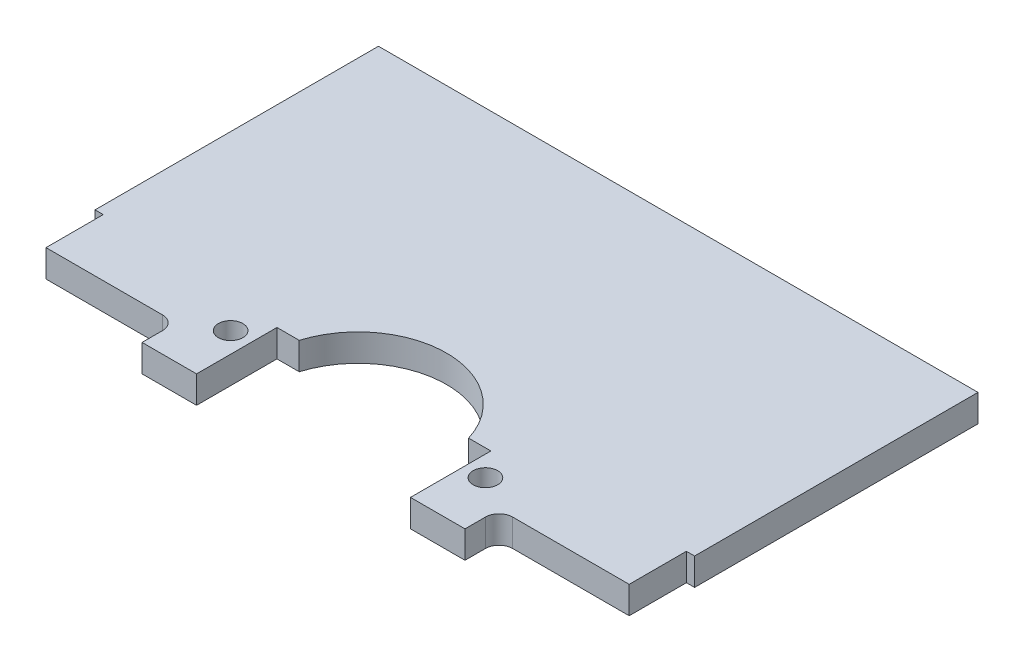
SolidWorks part; units mm, degrees
ref_plane "Front Plane" through (0, 0, 0) normal (0, 0, 1) x (1, 0, 0)
ref_plane "Top Plane" through (0, 0, 0) normal (0, 1, 0) x (1, 0, 0)
ref_plane "Right Plane" through (0, 0, 0) normal (1, 0, 0) x (0, 0, -1)
sketch "Sketch1" plane through (0, 0, 0) normal (0, 1, 0) x (1, 0, 0)
  line L0 (0, 0) -> (0, -20.1295) construction
  line L1 (-27.94, -13.208) -> (27.94, -13.208)
  line L2 (-27.94, -13.208) -> (-27.94, 13.208)
  line L3 (-27.94, 13.208) -> (27.94, 13.208)
  line L4 (27.94, -13.208) -> (27.94, 13.208)
  line L5 (-27.94, -13.208) -> (27.94, 13.208) construction
  line L6 (-27.94, 13.208) -> (27.94, -13.208) construction
  line L7 (-9.9695, -21.717) -> (-9.9695, -14.224)
  line L8 (-27.178, -18.542) -> (27.178, -18.542)
  line L9 (-27.178, -18.542) -> (-27.178, -13.208)
  line L10 (-27.178, -13.208) -> (27.178, -13.208)
  line L11 (27.178, -18.542) -> (27.178, -13.208)
  line L12 (-27.178, -18.542) -> (27.178, -13.208) construction
  line L13 (-27.178, -13.208) -> (27.178, -18.542) construction
  line L14 (-15.0495, -21.717) -> (15.0495, -21.717)
  line L15 (-15.0495, -21.717) -> (-15.0495, -18.542)
  line L16 (-15.0495, -18.542) -> (15.0495, -18.542)
  line L17 (15.0495, -21.717) -> (15.0495, -18.542)
  line L18 (-15.0495, -21.717) -> (15.0495, -18.542) construction
  line L19 (-15.0495, -18.542) -> (15.0495, -21.717) construction
  line L20 (-9.9695, -14.224) -> (9.9695, -14.224)
  line L21 (9.9695, -14.224) -> (9.9695, -21.717)
  line L22 (-11.8745, -21.717) -> (-11.8745, -16.637) construction
  line L23 (11.8745, -21.717) -> (11.8745, -16.637) construction
  line L24 (-11.8745, -16.637) -> (11.8745, -16.637) construction
  circle A0 centre (-11.8745, -16.637) radius 1.143
  circle A1 centre (11.8745, -16.637) radius 1.143
  arc A2 (-7.8945, -14.224) -> (7.8945, -14.224) centre (0, -16.637) cw
  point P0 (0, 0)
  point P8 (0, -15.875)
  dimension "D11" = 2.286
  dimension "D12" = 8.255
  dimension "D1" = 55.88
  dimension "D2" = 26.416
  dimension "D3" = 31.75
  dimension "D4" = 0.762
  dimension "D5" = 34.925
  dimension "D6" = 27.432
  dimension "D7" = 19.939
  dimension "D8" = 5.08
  dimension "D9" = 3.175
  dimension "D10" = 5.08
extrude "Boss-Extrude1" add sketch "Sketch1" along normal blind 2.54 contours L1 A2 L4 L3 L2 | L20 A2 L1 L9 L8 L7 A0 | L1 A2 L20 L21 L16 L8 L11 A1 | L15 L14 L7 L8 | L16 L21 L14 L17 region at (0, 0, -0.4105) region at (-18.6315, 0, 15.7849) region at (18.6315, 0, 15.7849) region at (-12.5095, 0, 20.1295) region at (12.5095, 0, 20.1295)
fillet "Fillet1" radius 1.27 2 edges at (-15.0495, 1.27, 18.542) (15.0495, 1.27, 18.542)
sketch "hours" plane through (0, 2.54, 0) normal (0, 1, 0) x (1, 0, 0)
  line L0 (0, 0) -> (0, -16.1969) construction
  line L1 (-17.3899, 1.193) -> (-15.3064, -0.8905)
  line L2 (15.3064, -0.8905) -> (17.3899, 1.193)
  line L3 (-7.4579, 1.808) -> (-8.5432, 4.4283)
  line L4 (7.4579, 1.808) -> (8.5432, 4.4283)
  line L5 (0, 2.6059) -> (0, 5.3999)
  line L6 (-13.7582, 1.7332) -> (-12.6317, 0.2651)
  line L7 (-10.9298, 2.7341) -> (-10.0169, 1.1528)
  line L8 (-5.4082, 3.9869) -> (-4.9448, 2.2574)
  line L9 (-2.6966, 4.2856) -> (-2.4641, 2.5197)
  line L10 (2.6966, 4.2856) -> (2.4641, 2.5197)
  line L11 (5.4082, 3.9869) -> (4.9448, 2.2574)
  line L12 (10.9298, 2.7341) -> (10.0169, 1.1528)
  line L13 (13.7582, 1.7332) -> (12.6317, 0.2651)
  line L31 (-27.94, -13.208) -> (-27.178, -13.208)
  line L32 (-27.178, -13.208) -> (-27.178, -18.542)
  line L33 (-27.178, -18.542) -> (-16.3195, -18.542)
  line L34 (-15.0495, -19.812) -> (-15.0495, -21.717)
  line L35 (-15.0495, -21.717) -> (-9.9695, -21.717)
  line L36 (-9.9695, -21.717) -> (-9.9695, -14.224)
  line L37 (-9.9695, -14.224) -> (-7.8945, -14.224)
  line L38 (7.8945, -14.224) -> (9.9695, -14.224)
  line L39 (9.9695, -14.224) -> (9.9695, -21.717)
  line L40 (9.9695, -21.717) -> (15.0495, -21.717)
  line L41 (15.0495, -21.717) -> (15.0495, -19.812)
  line L42 (16.3195, -18.542) -> (27.178, -18.542)
  line L43 (27.178, -18.542) -> (27.178, -13.208)
  line L44 (27.178, -13.208) -> (27.94, -13.208)
  line L45 (27.94, -13.208) -> (27.94, 13.208)
  line L46 (27.94, 13.208) -> (-27.94, 13.208)
  line L47 (-27.94, 13.208) -> (-27.94, -13.208)
  line L48 (-27.94, -13.208) -> (-27.178, -13.208)
  line L49 (-27.178, -13.208) -> (-27.178, -18.542)
  line L50 (-27.178, -18.542) -> (-16.3195, -18.542)
  line L51 (-15.0495, -19.812) -> (-15.0495, -21.717)
  line L52 (-15.0495, -21.717) -> (-9.9695, -21.717)
  line L53 (-9.9695, -21.717) -> (-9.9695, -14.224)
  line L54 (-9.9695, -14.224) -> (-7.8945, -14.224)
  line L55 (7.8945, -14.224) -> (9.9695, -14.224)
  line L56 (9.9695, -14.224) -> (9.9695, -21.717)
  line L57 (9.9695, -21.717) -> (15.0495, -21.717)
  line L58 (15.0495, -21.717) -> (15.0495, -19.812)
  line L59 (16.3195, -18.542) -> (27.178, -18.542)
  line L60 (27.178, -18.542) -> (27.178, -13.208)
  line L61 (27.178, -13.208) -> (27.94, -13.208)
  line L62 (27.94, -13.208) -> (27.94, 13.208)
  line L63 (27.94, 13.208) -> (-27.94, 13.208)
  line L64 (-27.94, 13.208) -> (-27.94, -13.208)
  arc A0 (-14.7549, -2.0345) -> (14.7549, -2.0345) centre (0, -32.6457) cw
  arc A1 (-15.3064, -0.8905) -> (15.3064, -0.8905) centre (0, -32.6457) cw
  arc A2 (-17.3899, 1.193) -> (17.3899, 1.193) centre (0, -32.6457) cw
  arc A3 (-16.5195, 1.6264) -> (16.5195, 1.6264) centre (0, -32.6457) cw construction
  arc A4 (-16.0784, 0.7111) -> (16.0784, 0.7111) centre (0, -32.6457) cw
  circle A5 centre (-11.8745, -16.637) radius 1.143 construction
  circle A6 centre (11.8745, -16.637) radius 1.143 construction
  circle A7 centre (-11.8745, -16.637) radius 1.143
  arc A8 (-15.0495, -19.812) -> (-16.3195, -18.542) centre (-16.3195, -19.812) ccw
  arc A9 (7.8945, -14.224) -> (-7.8945, -14.224) centre (0, -16.637) ccw
  arc A10 (16.3195, -18.542) -> (15.0495, -19.812) centre (16.3195, -19.812) ccw
  arc A11 (-15.0495, -19.812) -> (-16.3195, -18.542) centre (-16.3195, -19.812) ccw
  arc A12 (7.8945, -14.224) -> (-7.8945, -14.224) centre (0, -16.637) ccw
  arc A13 (16.3195, -18.542) -> (15.0495, -19.812) centre (16.3195, -19.812) ccw
  circle A14 centre (11.8745, -16.637) radius 1.143
  dimension "D1" = 33.9816
  dimension "D3" = 16.4488
  dimension "D5" = 22.5
  dimension "D6" = 22.5
  dimension "D7" = 22.5
  dimension "D8" = 1.778
  dimension "D9" = 7.5
  dimension "D10" = 7.5
  dimension "D11" = 7.5
  dimension "D12" = 7.5
  dimension "D13" = 7.5
  dimension "D14" = 7.5
  dimension "D15" = 7.5
  dimension "D16" = 7.5
  dimension "D2" = 1.27
  dimension "D4" = 2.794
  dimension "D17" = 0
sketch "minutes" plane through (0, 0, 0) normal (0, 1, 0) x (1, 0, 0)
  line L0 (0, 0) -> (0, -16.1969) construction
  line L1 (-17.3899, 1.193) -> (-15.3064, -0.8905)
  line L2 (15.3064, -0.8905) -> (17.3899, 1.193)
  line L3 (-4.9448, 2.2574) -> (-5.6729, 4.9746)
  line L4 (-8.1488, 3.4762) -> (-7.4579, 1.808)
  line L5 (0, 2.6059) -> (0, 5.3999)
  line L6 (-13.7582, 1.7332) -> (-12.6317, 0.2651)
  line L7 (-11.4505, 3.6359) -> (-10.0169, 1.1528)
  line L8 (2.6966, 4.2856) -> (2.4641, 2.5197)
  line L9 (-2.6966, 4.2856) -> (-2.4641, 2.5197)
  line L10 (4.9448, 2.2574) -> (5.6729, 4.9746)
  line L11 (8.1488, 3.4762) -> (7.4579, 1.808)
  line L12 (11.4505, 3.6359) -> (10.0169, 1.1528)
  line L13 (13.7582, 1.7332) -> (12.6317, 0.2651)
  line L14 (17.3899, 1.193) -> (15.3064, -0.8905)
  line L48 (-27.94, -13.208) -> (-27.178, -13.208)
  line L49 (-27.178, -13.208) -> (-27.178, -18.542)
  line L50 (-27.178, -18.542) -> (-16.3195, -18.542)
  line L51 (-15.0495, -19.812) -> (-15.0495, -21.717)
  line L52 (-15.0495, -21.717) -> (-9.9695, -21.717)
  line L53 (-9.9695, -21.717) -> (-9.9695, -14.224)
  line L54 (-9.9695, -14.224) -> (-7.8945, -14.224)
  line L55 (7.8945, -14.224) -> (9.9695, -14.224)
  line L56 (9.9695, -14.224) -> (9.9695, -21.717)
  line L57 (9.9695, -21.717) -> (15.0495, -21.717)
  line L58 (15.0495, -21.717) -> (15.0495, -19.812)
  line L59 (16.3195, -18.542) -> (27.178, -18.542)
  line L60 (27.178, -18.542) -> (27.178, -13.208)
  line L61 (27.178, -13.208) -> (27.94, -13.208)
  line L62 (27.94, -13.208) -> (27.94, 13.208)
  line L63 (27.94, 13.208) -> (-27.94, 13.208)
  line L64 (-27.94, 13.208) -> (-27.94, -13.208)
  arc A0 (-14.7549, -2.0345) -> (14.7549, -2.0345) centre (0, -32.6457) cw
  arc A1 (-15.3064, -0.8905) -> (15.3064, -0.8905) centre (0, -32.6457) cw
  arc A2 (-17.3899, 1.193) -> (17.3899, 1.193) centre (0, -32.6457) cw
  arc A3 (-16.5195, 1.6264) -> (16.5195, 1.6264) centre (0, -32.6457) cw construction
  arc A4 (-16.6343, 0.4374) -> (16.6343, 0.4374) centre (0, -32.6457) cw
  arc A5 (-16.0784, 0.7111) -> (16.0784, 0.7111) centre (0, -32.6457) cw construction
  circle A7 centre (-11.8745, -16.637) radius 1.143
  arc A11 (-15.0495, -19.812) -> (-16.3195, -18.542) centre (-16.3195, -19.812) ccw
  arc A12 (7.8945, -14.224) -> (-7.8945, -14.224) centre (0, -16.637) ccw
  arc A13 (16.3195, -18.542) -> (15.0495, -19.812) centre (16.3195, -19.812) ccw
  circle A14 centre (11.8745, -16.637) radius 1.143
  dimension "D1" = 33.9816
  dimension "D3" = 16.4488
  dimension "D5" = 15
  dimension "D6" = 15
  dimension "D7" = 15
  dimension "D8" = 1.778
  dimension "D9" = 7.5
  dimension "D10" = 7.5
  dimension "D11" = 7.5
  dimension "D2" = 1.27
  dimension "D4" = 2.794
